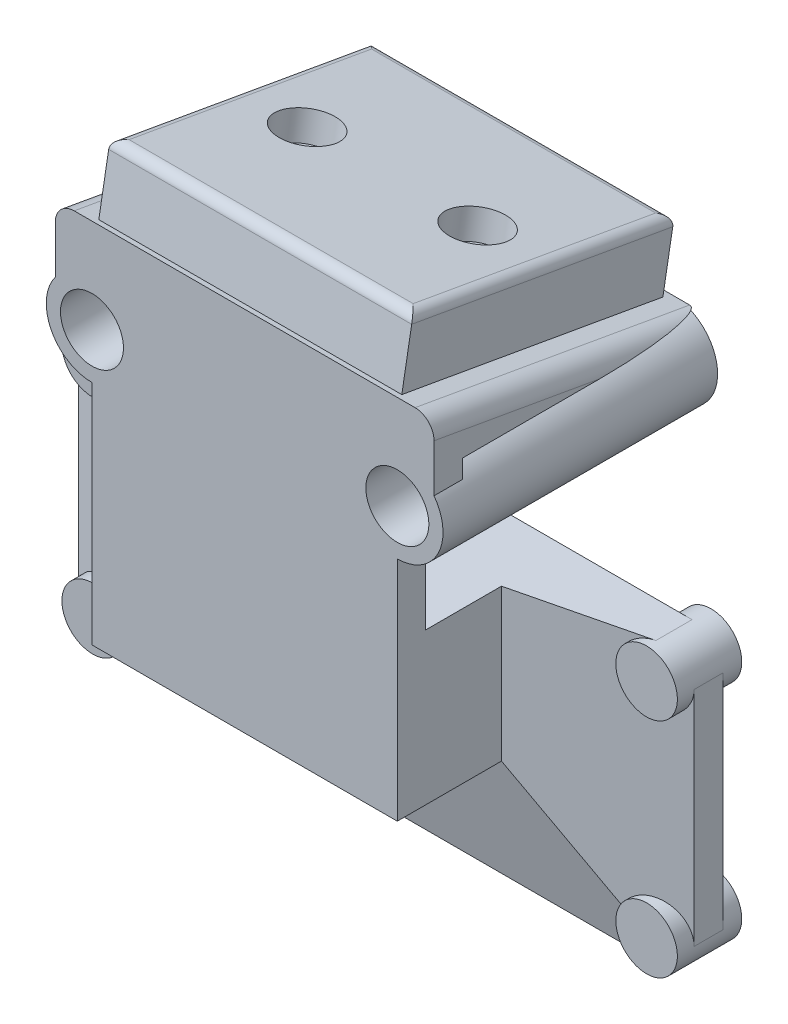
SolidWorks part; units mm, degrees
ref_plane "Спереди" through (0, 0, 0) normal (0, 0, 1) x (1, 0, 0)
ref_plane "Сверху" through (0, 0, 0) normal (0, 1, 0) x (1, 0, 0)
ref_plane "Справа" through (0, 0, 0) normal (1, 0, 0) x (0, 0, -1)
other "Configuration Table"
sketch "Эскиз1" plane through (0, 0, 0) normal (0, 0, 1) x (1, 0, 0)
  line L0 (0, -27.4594) -> (0, 30.9211) construction
  line L1 (12.8, 0) -> (0, 0) construction
  circle A0 centre (16.125, 0) radius 3.325
  circle A1 centre (16.125, 0) radius 4.825
  circle A2 centre (-16.125, 0) radius 3.325
  circle A3 centre (-16.125, 0) radius 4.825
  dimension "D1" = 1.5
  dimension "D3" = 6.65
  dimension "D2" = 12.8
extrude "Бобышка-Вытянуть1" add sketch "Эскиз1" along normal blind 29
sketch "Эскиз4" plane through (0, 0, 0) normal (1, 0, 0) x (0, 0, -1)
  line L0 (-29, 4.825) -> (-29, 9.9385)
  line L1 (-29, 9.9385) -> (0, 4.825)
  line L3 (0, 4.825) -> (-29, 4.825) construction
  line L4 (-29, 4.825) -> (0, 4.825)
  dimension "D1" = 10
  dimension "D2" = 29
extrude "Бобышка-Вытянуть2" add sketch "Эскиз4" along normal blind 20 and the other way blind 20 separate body
fillet "Скругление2" radius 2 2 edges at (20, 7.3817, 14.5) (-20, 7.3817, 14.5)
sketch "Эскиз6" plane through (0, 4.6795, -0.8251) normal (0, 0.9848, -0.1736) x (1, 0, 0)
  line L0 (0, -15.6794) -> (-11.1213, -15.6794) construction
  line L1 (-18, -0.8379) -> (18, -0.8379)
  line L2 (-18, -0.8379) -> (-18, -30.2852)
  line L3 (-18, -30.2852) -> (18, -30.2852)
  line L4 (18, -0.8379) -> (18, -30.2852)
  line L5 (-18, -0.8379) -> (18, -0.8379)
  line L6 (-18, -0.8379) -> (-18, -32.8379)
  line L7 (-18, -32.8379) -> (18, -32.8379)
  line L8 (18, -0.8379) -> (18, -32.8379)
  line L9 (0, -15.6794) -> (0, 5.0301) construction
  line L10 (-16, -29.6794) -> (16, -29.6794)
  line L11 (-16, -29.6794) -> (-16, -1.6794)
  line L12 (-16, -1.6794) -> (16, -1.6794)
  line L13 (16, -29.6794) -> (16, -1.6794)
  line L14 (-16, -29.6794) -> (16, -1.6794) construction
  line L15 (-16, -1.6794) -> (16, -29.6794) construction
  point P8 (0, -15.6794)
  point P19 (0, -2.0764)
  point P22 (5.566, -2.0764)
  dimension "D1" = 28
  dimension "D2" = 32
  dimension "D3" = 32
sketch "Эскиз10" plane through (0, 0, 0) normal (0, 0, -1) x (-1, 0, 0)
  line L0 (18, 4.825) -> (-18, 4.825) construction
  line L1 (-16.125, 4.825) -> (16.125, 4.825)
  line L2 (-16.125, 4.825) -> (-16.125, 3.325)
  line L3 (-16.125, 3.325) -> (16.125, 3.325)
  line L4 (16.125, 4.825) -> (16.125, 3.325)
  circle A0 centre (-16.125, 0) radius 4.825 construction
  circle A1 centre (16.125, 0) radius 3.325 construction
  dimension "D1" = 1.5
extrude "Бобышка-Вытянуть11" add sketch "Эскиз10" against normal blind 29
extrude "Бобышка-Вытянуть13" add sketch "Эскиз6" along normal blind 7 contours L10 L13 L12 L11 region at (0, 7.4022, 14.6161)
fillet "Скругление3" radius 1 4 edges at (0, 16.7269, 27.1878) (16, 14.2959, 13.4005) (0, 11.8648, -0.3868) (-16, 14.2959, 13.4005)
sketch "Эскиз11" plane through (0, 11.5732, -2.0407) normal (0, 0.9848, -0.1736) x (1, 0, 0)
  line L0 (-15, -15.6794) -> (15, -15.6794) construction
  line L1 (-15, -2.6794) -> (-15, -28.6794) construction
  line L2 (15, -28.6794) -> (15, -2.6794) construction
  circle A0 centre (-9, -15.6794) radius 3
  circle A1 centre (9, -15.6794) radius 3
  dimension "D1" = 6
  dimension "D2" = 6
  dimension "D3" = 6
  dimension "D4" = 6
extrude "Вырез-Вытянуть1" cut sketch "Эскиз11" against normal blind 3
sketch "Эскиз12" plane through (0, 0, 29) normal (0, 0, 1) x (1, 0, 0)
  line L0 (-20, 4.825) -> (-20, 2.8749)
  line L1 (20, 4.825) -> (20, 2.8749)
  line L2 (-12.6286, 3.325) -> (12.6286, 3.325)
  line L3 (-16.125, -4.825) -> (16.125, -4.825)
  line L4 (20, 4.825) -> (16.125, 4.825)
  line L5 (-16.125, 4.825) -> (-20, 4.825)
  arc A0 (-16.125, 4.825) -> (-20, 2.8749) centre (-16.125, 0) ccw
  arc A1 (20, 2.8749) -> (16.125, 4.825) centre (16.125, 0) ccw
  arc A2 (16.125, 4.825) -> (20, 2.8749) centre (16.125, 0) cw
  arc A3 (-16.125, 4.825) -> (-20, 2.8749) centre (-16.125, 0) ccw
  arc A4 (-12.6286, 3.325) -> (-16.125, -4.825) centre (-16.125, 0) cw
  arc A5 (12.6286, 3.325) -> (16.125, -4.825) centre (16.125, 0) ccw
  arc M5 (12.6286, 3.325) -> (16.125, 4.825) centre (16.125, 0) ccw
  line M6 (16.125, 4.825) -> (20, 4.825)
  line M12 (-20, 4.825) -> (-16.125, 4.825)
  arc M13 (-16.125, 4.825) -> (-12.6286, 3.325) centre (-16.125, 0) ccw
  line M14 (-12.6286, 3.325) -> (12.6286, 3.325)
extrude "Бобышка-Вытянуть14" add sketch "Эскиз12" against normal blind 3 contours L3 M13 M5 M14 | L1 M6 M5 | L0 M12 M13 region at (-19.0747, 4.2678, 29) region at (19.0747, 4.2678, 29) region at (0, -0.8562, 29)
sketch "Эскиз13" plane through (0, -4.825, 0) normal (0, -1, 0) x (1, 0, 0)
  line L0 (-16.125, 29) -> (-16.125, 26)
  line L1 (-16.125, 26) -> (16.125, 26)
  line L2 (16.125, 26) -> (16.125, 29)
  line L3 (16.125, 29) -> (-16.125, 29)
extrude "Бобышка-Вытянуть15" add sketch "Эскиз13" along normal blind 24
sketch "Эскиз14" plane through (0, 0, 26) normal (0, 0, -1) x (-1, 0, 0)
  line L0 (16.125, -28.825) -> (16.125, -4.825) construction
  line L1 (-16.125, -28.825) -> (16.125, -28.825)
  line L2 (-16.125, -28.825) -> (-16.125, -12.825)
  line L3 (-16.125, -12.825) -> (16.125, -12.825)
  line L4 (16.125, -28.825) -> (16.125, -12.825)
  dimension "D1" = 8
extrude "Бобышка-Вытянуть16" add sketch "Эскиз14" along normal blind 12 separate body
sketch "Эскиз15" plane through (0, 0, 14) normal (0, 0, -1) x (-1, 0, 0)
  line L0 (0, -12.825) -> (0, -28.825) construction
  line L1 (16.125, -12.825) -> (-16.125, -12.825) construction
  line L2 (-16.125, -28.825) -> (16.125, -28.825) construction
  line L4 (-32.5, -42.825) -> (32.5, -42.825)
  line L5 (-32.5, -42.825) -> (-32.5, -12.825)
  line L6 (-32.5, -12.825) -> (32.5, -12.825)
  line L7 (32.5, -42.825) -> (32.5, -12.825)
  line L8 (0, -12.825) -> (0, -42.825) construction
  line L9 (-32.5, -27.825) -> (32.5, -27.825) construction
  point P6 (0, -27.825)
  dimension "D1" = 65
  dimension "D2" = 30
extrude "Бобышка-Вытянуть17" add sketch "Эскиз15" along normal blind 3
sketch "Эскиз16" plane through (0, 0, 11) normal (0, 0, -1) x (-1, 0, 0)
  line L0 (32.5, -12.825) -> (-32.5, -12.825) construction
  line L2 (32.5, -42.825) -> (32.5, -12.825) construction
  circle A0 centre (29.25, -16.075) radius 3.25
  circle A1 centre (-29.25, -16.075) radius 3.25
  circle A2 centre (29.25, -39.575) radius 3.25
  circle A3 centre (-29.25, -39.575) radius 3.25
  dimension "D1" = 2
  dimension "D4" = 6.5
  dimension "D5" = 58.5
  dimension "D6" = 23.5
  dimension "D2" = 2
  dimension "D3" = 2
extrude "Бобышка-Вытянуть18" add sketch "Эскиз16" along normal blind 2
sketch "Эскиз17" plane through (0, 0, 11) normal (0, 0, -1) x (-1, 0, 0)
  line L3 (-32.5, -42.825) -> (-29.25, -42.825) construction
  line L9 (-32.5, -16.075) -> (-32.5, -39.575)
  line L10 (-29.25, -12.825) -> (29.25, -12.825)
  line L11 (32.5, -16.075) -> (32.5, -39.575)
  line L12 (29.25, -42.825) -> (-29.25, -42.825)
  line L14 (-34.5091, -11.7001) -> (34.0547, -11.7001)
  line L15 (-34.5091, -11.7001) -> (-34.5091, -44.2679)
  line L16 (-34.5091, -44.2679) -> (34.0547, -44.2679)
  line L17 (34.0547, -11.7001) -> (34.0547, -44.2679)
  arc A0 (-32.5, -16.075) -> (-29.25, -12.825) centre (-29.25, -16.075) cw
  circle A1 centre (-29.25, -16.075) radius 3.25 construction
  circle A2 centre (-29.25, -39.575) radius 3.25 construction
  arc A3 (-32.5, -39.575) -> (-29.25, -42.825) centre (-29.25, -39.575) ccw
  arc A4 (32.5, -39.575) -> (29.25, -42.825) centre (29.25, -39.575) cw
  arc A5 (29.25, -12.825) -> (32.5, -16.075) centre (29.25, -16.075) cw
extrude "Вырез-Вытянуть2" cut sketch "Эскиз17" against normal blind 6
sketch "Эскиз18" plane through (16.125, 0, 0) normal (1, 0, 0) x (0, 0, -1)
  line L0 (-14, -12.825) -> (-18, -12.825)
  line L1 (-14, -12.825) -> (-26, -12.825) construction
  line L2 (-18, -12.825) -> (-18, -28.825)
  line L3 (-14, -28.825) -> (-29, -28.825) construction
  line L4 (-18, -28.825) -> (-14, -28.825)
  line L5 (-14, -28.825) -> (-14, -12.825)
  dimension "D1" = 4
extrude "Бобышка-Вытянуть19" add sketch "Эскиз18" along normal blind 16.5
sketch "Эскиз19" plane through (-16.125, 0, 0) normal (-1, 0, 0) x (0, 0, 1)
  line L0 (14, -12.825) -> (18, -12.825)
  line L1 (14, -12.825) -> (26, -12.825) construction
  line L2 (18, -12.825) -> (18, -28.825)
  line L3 (18, -28.825) -> (14, -28.825)
  line L4 (14, -28.825) -> (14, -12.825)
extrude "Бобышка-Вытянуть20" add sketch "Эскиз19" along normal blind 16.5
sketch "Эскиз20" plane through (0, -28.825, 0) normal (0, -1, 0) x (1, 0, 0)
  line L8 (-16.125, 18) -> (-32.625, 18)
  line L9 (-32.625, 18) -> (-32.625, 14)
  line L10 (-32.625, 14) -> (-16.125, 18)
  line L11 (16.125, 18) -> (32.625, 18)
  line L12 (32.625, 18) -> (32.625, 14)
  line L13 (32.625, 14) -> (16.125, 18)
extrude "Вырез-Вытянуть4" cut sketch "Эскиз20" against normal blind 17
sketch "Эскиз21" plane through (0, -28.825, 0) normal (0, -1, 0) x (1, 0, 0)
  line L0 (-32.625, 14) -> (-16.125, 18)
  line L1 (-16.125, 18) -> (16.125, 18)
  line L3 (32.625, 14) -> (-32.625, 14)
  line L4 (32.625, 14) -> (32.5, 14) construction
  line L5 (32.625, 14) -> (16.125, 18)
extrude "Бобышка-Вытянуть21" add sketch "Эскиз21" along normal blind 15
sketch "Эскиз22" plane through (-16.125, 0, 0) normal (-1, 0, 0) x (0, 0, 1)
  line L0 (18, -28.825) -> (18, -43.825)
  line L1 (18, -43.825) -> (14, -43.825)
  line L2 (14, -43.825) -> (18, -28.825)
extrude "Вырез-Вытянуть5" cut sketch "Эскиз22" against normal blind 55 and the other way blind 25
sketch "Эскиз23" plane through (0, 0, 11) normal (0, 0, -1) x (-1, 0, 0)
  line L8 (-29.25, -12.825) -> (29.25, -12.825)
  line L9 (32.5, -16.075) -> (32.5, -39.575)
  line L10 (29.25, -42.825) -> (-29.25, -42.825)
  line L11 (-32.5, -39.575) -> (-32.5, -16.075)
  line L13 (-35.3967, -10.0588) -> (34.8073, -10.0588)
  line L14 (-35.3967, -10.0588) -> (-35.3967, -46.5403)
  line L15 (-35.3967, -46.5403) -> (34.8073, -46.5403)
  line L16 (34.8073, -10.0588) -> (34.8073, -46.5403)
  circle A4 centre (29.25, -16.075) radius 3.25 construction
  arc A5 (29.25, -12.825) -> (32.5, -16.075) centre (29.25, -16.075) ccw construction
  arc A6 (29.25, -12.825) -> (32.5, -16.075) centre (29.25, -16.075) cw
  arc A7 (32.5, -39.575) -> (29.25, -42.825) centre (29.25, -39.575) cw
  circle A8 centre (-29.25, -39.575) radius 3.25 construction
  arc A9 (-32.5, -39.575) -> (-29.25, -42.825) centre (-29.25, -39.575) ccw construction
  arc A10 (-29.25, -42.825) -> (-32.5, -39.575) centre (-29.25, -39.575) cw
  arc A11 (-32.5, -16.075) -> (-29.25, -12.825) centre (-29.25, -16.075) cw
extrude "Вырез-Вытянуть6" cut sketch "Эскиз23" against normal blind 5
extrude "Бобышка-Вытянуть22" add sketch "Эскиз16<2>" against normal blind 4.8
sketch "Эскиз16<2>" plane through (0, 0, 11) normal (0, 0, -1) x (-1, 0, 0) same geometry as "Эскиз16"
